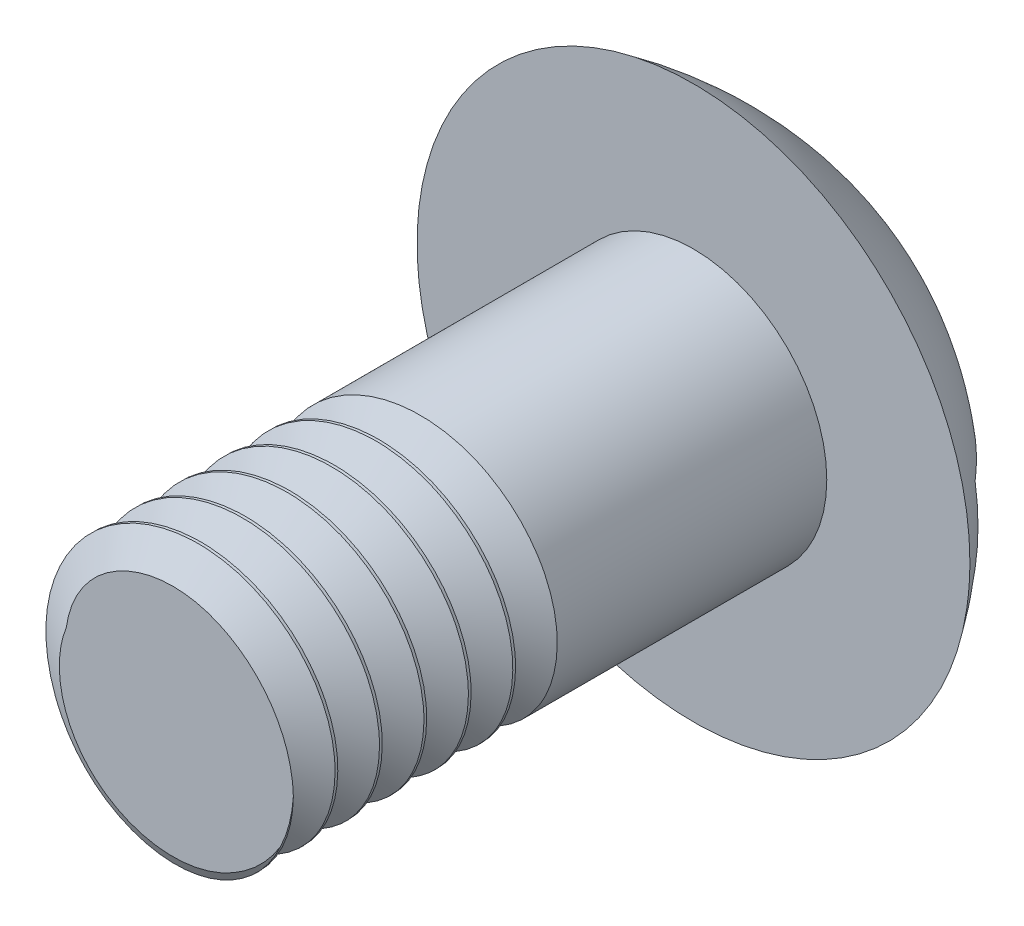
SolidWorks part; units mm, degrees
material "AISI 304"
ref_plane "Front" through (0, 0, 0) normal (0, 0, 1) x (1, 0, 0)
ref_plane "Top" through (0, 0, 0) normal (0, 1, 0) x (1, 0, 0)
ref_plane "Right" through (0, 0, 0) normal (1, 0, 0) x (0, 0, -1)
sketch "Sketch1" plane through (0, 0, 0) normal (0, 0, 1) x (1, 0, 0)
  circle A0 centre (0, 0) radius 1.5
  dimension "D1" = 3
extrude "Boss-Extrude1" add sketch "Sketch1" along normal blind 6
sketch "Sketch2" plane through (0, 0, 6) normal (0, 0, 1) x (1, 0, 0)
  circle A0 centre (0, 0) radius 1.5 construction
  circle A1 centre (0, 0) radius 1.5
curve "Helix/Spiral1" pitch 0.5 height 3 radius 1.5 centre (0, 0, 6) axis (0, 0, -1) start towards (-1, 0, 0)
ref_plane "Plane1" through (-1.5, 0, 6) normal (0, 0.9986, -0.053) x (1, 0, 0)
sketch "Sketch3" plane through (-1.5, 0, 6) normal (0, 0.9986, -0.053) x (1, 0, 0)
  line L1 (0.4058, -0.0197) -> (-0.0099, 0.2203)
  line L2 (-0.0099, 0.2203) -> (-0.0099, -0.2597)
  line L3 (-0.0099, -0.2597) -> (0.4058, -0.0197)
  circle A0 centre (0.1287, -0.0197) radius 0.1386 construction
  dimension "D1" = 0.48
sweep "Cut-Sweep1" cut profiles "Sketch3" path "Helix/Spiral1" align with end faces yes
sketch "Sketch4" plane through (0, 0, 0) normal (1, 0, 0) x (0, 0, -1)
  line L0 (0, 0) -> (1.8274, 0) construction
  line L1 (0, -3.1105) -> (0, 0)
  line L2 (0, 0) -> (1.8274, 0)
  spline S0 degree 2 poles (1.8274, 0) (1.6148, -1.9936) (0, -3.1105) knots 0 0 0 1 1 1
  point P4 (0, -3.1105)
  point P6 (1.1493, -1.9583)
revolve "Revolve1" add sketch "Sketch4" angle 360 about L0
ref_plane "Plane2" through (0, 0, -0.3966) normal (0, 0, 1) x (1, 0, 0)
sketch "Sketch5" plane through (0, 0, -0.3966) normal (0, 0, 1) x (1, 0, 0)
  line L0 (0, 0) -> (3.4863, 0) construction
  line L1 (-5.3817, -0.425) -> (6.1104, -0.425)
  line L2 (-5.3817, -0.425) -> (-5.3817, 0.425)
  line L3 (-5.3817, 0.425) -> (6.1104, 0.425)
  line L4 (6.1104, -0.425) -> (6.1104, 0.425)
  point P7 (6.1104, 0)
  dimension "D1" = 0.85
extrude "Cut-Extrude1" cut sketch "Sketch5" against normal blind 2
